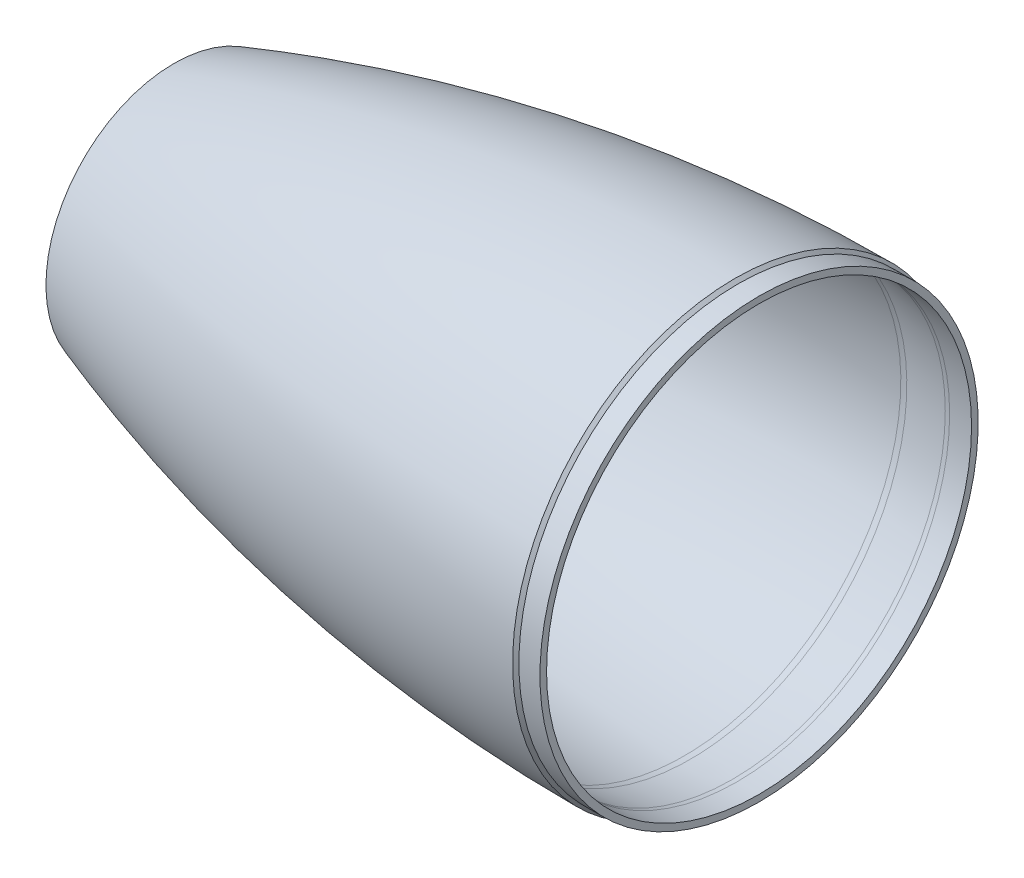
SolidWorks part; units mm, degrees
ref_plane "Front Plane" through (0, 0, 0) normal (0, 0, 1) x (1, 0, 0)
ref_plane "Top Plane" through (0, 0, 0) normal (0, 1, 0) x (1, 0, 0)
ref_plane "Right Plane" through (0, 0, 0) normal (1, 0, 0) x (0, 0, -1)
sketch "Sketch1" plane through (0, 0, 0) normal (0, 0, 1) x (1, 0, 0)
  line L4 (0, 0) -> (-304.8, 0) construction
  line L9 (0, 76.975) -> (0, 0) construction
  line L10 (0, 80.518) -> (50.8, 80.518) construction
  line L11 (-203.2, 46.355) -> (-203.2, 41.4655)
  line L12 (-203.2, 41.4655) -> (-193.1303, 41.4655)
  line L14 (-188.6401, 43.3254) -> (-181.0842, 50.8813)
  line L15 (1.143, 79.375) -> (8.763, 79.375)
  line L16 (0, 80.518) -> (1.143, 79.375)
  line L17 (0.8317, 76.975) -> (8.763, 76.975)
  line L18 (8.763, 76.975) -> (8.763, 79.375)
  line L19 (-0.8286, 77.0475) -> (-16.0937, 78.383)
  arc A4 (0, 80.518) -> (-203.2, 46.355) centre (0, -540.8758) ccw
  arc A5 (-18.3172, 78.4472) -> (-178.4227, 52.4722) centre (0, -540.8758) ccw
  arc A6 (0, 78.718) -> (-202.6114, 44.654) centre (0, -540.8758) ccw construction
  arc A9 (-16.0937, 78.383) -> (-18.3172, 78.4472) centre (-17.754, 59.4055) ccw
  arc A10 (-0.8286, 77.0475) -> (0.8317, 76.975) centre (0.8317, 96.025) ccw
  arc A11 (-193.1303, 41.4655) -> (-188.6401, 43.3254) centre (-193.1303, 47.8155) ccw
  arc A12 (-178.4227, 52.4722) -> (-181.0842, 50.8813) centre (-176.5941, 46.3912) ccw
  point P6 (-183.3126, 50.9797)
  point P8 (-57.2734, -19.8104)
  point P9 (0, 313.4439)
  point P10 (-150.9565, 274.6984)
  point P18 (-183.2411, 51.0019)
  point P21 (-190.5, 41.4655)
  point P24 (-172.0085, 54.3633)
  dimension "D7" = 12.7
  dimension "D10" = 6.35
  dimension "D17" = 19.05
  dimension "D8" = 135
  dimension "D1" = 161.036
  dimension "D2" = 50.8
  dimension "D3" = 203.2
  dimension "D4" = 92.71
  dimension "D6" = 82.931
  dimension "D9" = 304.8
  dimension "D12" = 7.62
  dimension "D13" = 158.75
  dimension "D14" = 45
  dimension "D15" = 2.4
  dimension "D16" = 175
  dimension "D5" = 1.8
revolve "Revolve1" add sketch "Sketch1" angle 360 about L4
